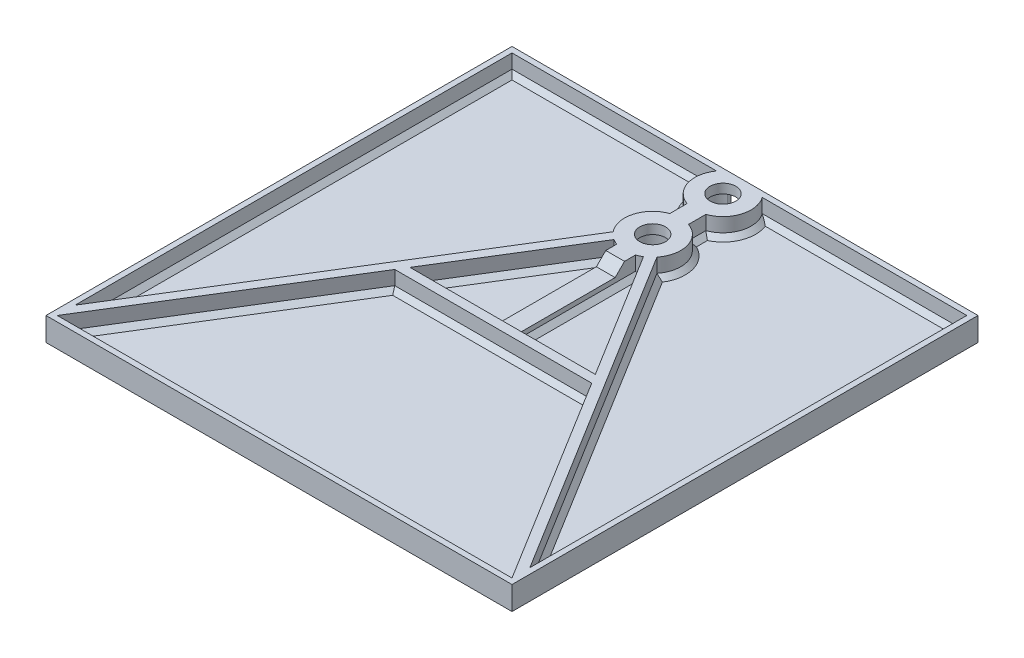
SolidWorks part; units mm, degrees
ref_plane "前视基准面" through (0, 0, 0) normal (0, 0, 1) x (1, 0, 0)
ref_plane "上视基准面" through (0, 0, 0) normal (0, 1, 0) x (1, 0, 0)
ref_plane "右视基准面" through (0, 0, 0) normal (1, 0, 0) x (0, 0, -1)
other "Configuration Table"
sketch "草图1" plane through (0, 0, 0) normal (0, 1, 0) x (1, 0, 0)
  line L0 (-45, 45) -> (45, 45) construction
  line L1 (-50, 50) -> (50, 50)
  line L2 (-50, 50) -> (-50, -50)
  line L3 (-50, -50) -> (50, -50)
  line L4 (50, 50) -> (50, -50)
  line L5 (-50, 50) -> (50, -50) construction
  line L6 (-50, -50) -> (50, 50) construction
  line L7 (-30, -30) -> (30, -30) construction
  line L8 (-40, -40) -> (40, -40) construction
  line L9 (40, -40) -> (40, -20) construction
  line L11 (28, -31) -> (-24, -31)
  line L12 (28, -31) -> (28, -49)
  line L13 (28, -49) -> (-24, -49)
  line L14 (-24, -31) -> (-24, -49)
  circle A0 centre (-45, 45) radius 1.75
  circle A1 centre (45, 45) radius 1.75
  circle A2 centre (-30, -30) radius 1.75
  circle A3 centre (30, -30) radius 1.75
  circle A4 centre (-40, -40) radius 5
  circle A5 centre (40, -40) radius 5
  circle A6 centre (40, -20) radius 5
  point P0 (0, 0)
  dimension "D4" = 3.5
  dimension "D8" = 10
  dimension "D1" = 100
  dimension "D2" = 100
  dimension "D3" = 5
  dimension "D5" = 20
  dimension "D6" = 10
  dimension "D7" = 20
  dimension "D9" = 52
  dimension "D10" = 18
  dimension "D11" = 1
  dimension "D12" = 22
sketch "草图2" plane through (0, 0, 0) normal (0, 1, 0) x (1, 0, 0)
  line L1 (-50, 50) -> (50, 50)
  line L2 (-50, 50) -> (-50, -50)
  line L3 (-50, -50) -> (50, -50)
  line L4 (50, 50) -> (50, -50)
  line L5 (-50, 50) -> (50, -50) construction
  line L6 (-50, -50) -> (50, 50) construction
  point P0 (0, 0)
extrude "凸台-拉伸1" add sketch "草图2" against normal blind 2
sketch "草图3" plane through (0, 0, 0) normal (0, 1, 0) x (1, 0, 0)
  line L0 (0, 50) -> (0, 45) construction
  line L1 (-50, 50) -> (50, 50) construction
  line L2 (-45, 45) -> (45, 45) construction
  line L3 (0, 45) -> (0, 30) construction
  circle A0 centre (0, 45) radius 2.75
  circle A1 centre (0, 30) radius 2.75
  circle A2 centre (0, 45) radius 4.75
  circle A3 centre (0, 30) radius 4.75
  circle A4 centre (0, 45) radius 6
  circle A5 centre (0, 30) radius 6
  dimension "D2" = 5.5
  dimension "D3" = 9.5
  dimension "D4" = 12
  dimension "D1" = 15
extrude "切除-拉伸1" cut sketch "草图3" against normal through all contours A2 | A3
extrude "凸台-拉伸2" add sketch "草图3<3>" along normal blind 2 contours A4 A2 | A5 A3 region at (-5.8303, 0, -45) region at (-5.8303, 0, -30)
sketch "草图3<3>" plane through (0, 0, 0) normal (0, 1, 0) x (1, 0, 0) same geometry as "草图3"
extrude "凸台-拉伸3" add sketch "草图3<4>" along normal blind 2 from surface contours A4 A2 | A2 A0 | A5 A3 | A3 A1 region at (-4.6156, 0, -45) region at (-4.6156, 0, -30) region at (-5.8303, 0, -45) region at (-5.8303, 0, -30) starting at face at (0, 2, -40.25)
sketch "草图3<4>" plane through (0, 0, 0) normal (0, 1, 0) x (1, 0, 0) same geometry as "草图3"
sketch "草图5" plane through (0, 0, 0) normal (0, 1, 0) x (1, 0, 0)
  line L0 (-3.3166, 50) -> (3.3166, 50)
  circle A0 centre (0, 45) radius 6 construction
  arc A1 (3.3166, 50) -> (-3.3166, 50) centre (0, 45) ccw
  arc A2 (-3.3166, 50) -> (3.3166, 50) centre (0, 45) ccw construction
extrude "切除-拉伸2" cut sketch "草图5" along normal through all
sketch "草图6" plane through (0, 0, 0) normal (0, 1, 0) x (1, 0, 0)
  line L0 (-3.3166, 50) -> (-50, 50)
  line L1 (-50, 50) -> (-50, -50)
  line L2 (-50, -50) -> (50, -50)
  line L3 (50, -50) -> (50, 50)
  line L4 (50, 50) -> (3.3166, 50)
  line L5 (-48.5, 48.5) -> (-4.8734, 48.5)
  line L6 (-50, 50) -> (50, -50) construction
  line L7 (-50, -50) -> (50, 50) construction
  line L8 (48.5, 48.5) -> (48.5, -48.5)
  line L9 (48.5, -48.5) -> (-48.5, -48.5)
  line L10 (-48.5, -48.5) -> (-48.5, 48.5)
  line L11 (-4.8734, 48.5) -> (4.8734, 48.5) construction
  line L12 (4.8734, 48.5) -> (48.5, 48.5)
  arc A0 (-3.3166, 50) -> (3.3166, 50) centre (0, 45) ccw construction
  arc A1 (-3.3166, 50) -> (-4.8734, 48.5) centre (0, 45) ccw
  arc A2 (-4.8734, 48.5) -> (4.8734, 48.5) centre (0, 45) ccw construction
  arc A3 (4.8734, 48.5) -> (3.3166, 50) centre (0, 45) ccw
  dimension "D1" = 1.5
extrude "凸台-拉伸4" add sketch "草图6" along normal blind 4
sketch "草图8" plane through (0, 0, 0) normal (0, 1, 0) x (1, 0, 0)
  line L0 (2, 39.3431) -> (2, 35.6569)
  line L1 (2, 24.3431) -> (2, -2)
  line L3 (2, -2) -> (-2, -2) construction
  line L4 (-2, -2) -> (-2, 24.3431)
  line L5 (-2, 35.6569) -> (-2, 39.3431)
  line L6 (48.5, -48.5) -> (21.0064, -4)
  line L7 (48.5, -44.6949) -> (4.6747, 26.2388)
  line L8 (48.5, 48.5) -> (48.5, -48.5) construction
  line L9 (0, 0) -> (0, -2) construction
  line L10 (48.5, -44.6949) -> (48.5, -48.5)
  line L11 (-48.5, -44.6949) -> (-4.6747, 26.2388)
  line L12 (-48.5, -48.5) -> (-21.0064, -4)
  line L13 (-48.5, -44.6949) -> (-48.5, -48.5)
  line L14 (-2, -2) -> (-19.7707, -2)
  line L15 (2, -2) -> (19.7707, -2)
  line L16 (-21.0064, -4) -> (21.0064, -4)
  line L17 (-21.0064, -4) -> (-19.7707, -2) construction
  line L18 (-19.7707, -2) -> (-3.1536, 24.8956)
  line L19 (21.0064, -4) -> (19.7707, -2) construction
  line L20 (19.7707, -2) -> (3.1536, 24.8956)
  arc A1 (-4.8734, 48.5) -> (4.8734, 48.5) centre (0, 45) ccw construction
  arc A3 (-2, 39.3431) -> (2, 39.3431) centre (0, 45) ccw
  circle A5 centre (0, 30) radius 6 construction
  arc A6 (3.1536, 24.8956) -> (4.6747, 26.2388) centre (0, 30) ccw
  arc A7 (2, 35.6569) -> (-2, 35.6569) centre (0, 30) ccw
  arc A8 (-2, 24.3431) -> (2, 24.3431) centre (0, 30) ccw
  arc A9 (-3.1536, 24.8956) -> (-4.6747, 26.2388) centre (0, 30) cw
  point P16 (0, -2)
  dimension "D1" = 4
  dimension "D2" = 2
  dimension "D3" = 2
  dimension "D4" = 2
extrude "凸台-拉伸5" add sketch "草图8" along normal up to surface (4 mm away) up to face at (0, 4, -14.5833)
chamfer "倒角1" distance 1 angle 45 16 edges at (0, 0, 48.5) (-48.5, 0, -1.9026) (-26.6867, 0, -48.5) (5.7248, 0, -43.2036) (-5.7248, 0, -43.2036) (26.6867, 0, -48.5) (48.5, 0, -1.9026) (-26.5874, 0, 9.2281) (-2, 0, -37.5) (-5.7717, 0, -31.6392) (34.7532, 0, 26.25) (-34.7532, 0, 26.25) (0, 0, 4) (26.5874, 0, 9.2281) (5.7717, 0, -31.6392) (2, 0, -37.5)
chamfer "倒角4" distance 1 angle 45 6 edges at (2, 0, -11.1716) (10.8854, 0, 2) (11.4622, 0, -11.4478) (-11.4622, 0, -11.4478) (-10.8854, 0, 2) (-2, 0, -11.1716)
sketch "草图7" plane through (0, 0, 0) normal (0, 1, 0) x (1, 0, 0)
  line L1 (49.7, -49.7) -> (-49.7, -49.7)
  line L2 (49.7, -49.7) -> (49.7, 49.7)
  line L3 (49.7, 49.7) -> (-49.7, 49.7)
  line L4 (-49.7, -49.7) -> (-49.7, 49.7)
  line L5 (49.7, -49.7) -> (-49.7, 49.7) construction
  line L6 (49.7, 49.7) -> (-49.7, -49.7) construction
  line L7 (50, 50) -> (-50, 50) construction
  point P0 (0, 0)
  dimension "D1" = 0.3
extrude "切除-拉伸3" cut sketch "草图7" against normal through all both and the other way through all flip side to cut
fillet "圆角1" radius 0.5 2 edges at (-0.6874, 0, -49.7) (0.6874, 0, -49.7)
chamfer "倒角2" distance 1 angle 45 3 edges at (49.7, -2, 0) (0, -2, 49.7) (-49.7, -2, 0)
chamfer "倒角3" distance 1 angle 45 2 edges at (25.925, -2, -49.7) (-25.925, -2, -49.7) tangent propagation no
sketch "草图9" plane through (0, 0, 0) normal (0, 1, 0) x (1, 0, 0)
  line L0 (0, 30) -> (0, 10) construction
  line L1 (-6, 20) -> (6, 20)
  line L2 (-6, 20) -> (-6, 0)
  line L3 (-6, 0) -> (6, 0)
  line L4 (6, 20) -> (6, 0)
  line L5 (-6, 20) -> (6, 0) construction
  line L6 (-6, 0) -> (6, 20) construction
  point P0 (0, 10)
  dimension "D1" = 20
  dimension "D2" = 20
  dimension "D3" = 12
extrude "切除-拉伸4" cut sketch "草图9" against normal blind 2 from surface starting at face at (0, 4, -42.25)
chamfer "倒角5" distance 2 angle 45 2 edges at (0, 4, 0) (0, 4, -20)
